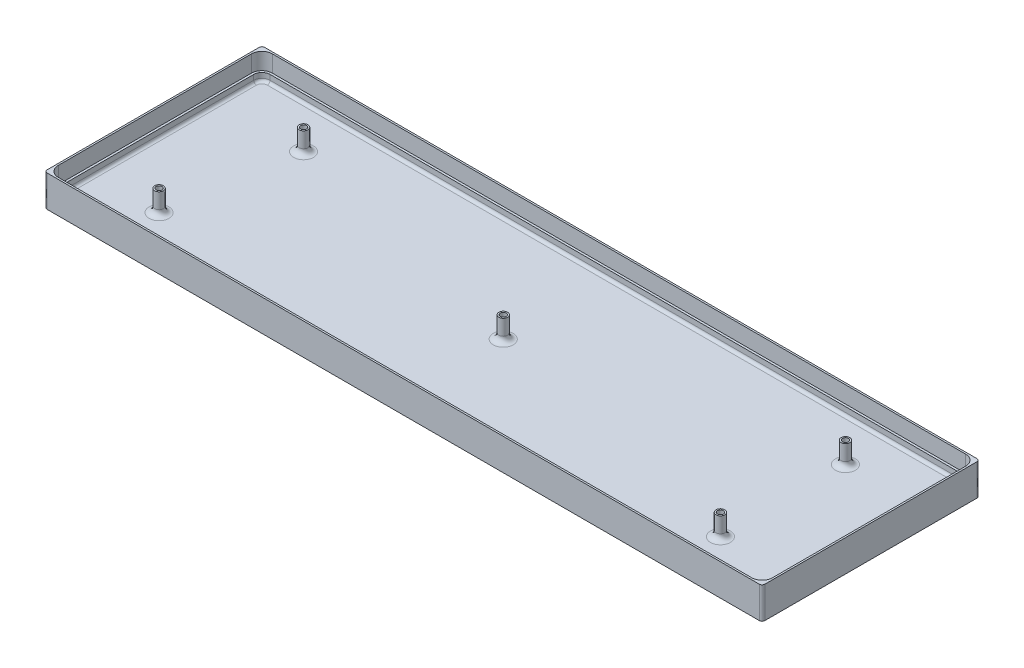
SolidWorks part; units mm, degrees
note: The reader was unsure of these and kept them because the rebuilt part matched: shared geometry of "Sketch1<3>".
ref_plane "Front Plane" through (0, 0, 0) normal (0, 0, 1) x (1, 0, 0)
ref_plane "Top Plane" through (0, 0, 0) normal (0, 1, 0) x (1, 0, 0)
ref_plane "Right Plane" through (0, 0, 0) normal (1, 0, 0) x (0, 0, -1)
sketch "Sketch1" plane through (0, 0, 0) normal (0, 1, 0) x (1, 0, 0)
  line L5 (163.576, 49.5808) -> (-163.576, 49.5808)
  line L6 (162.7759, -48.7807) -> (-162.7759, -48.7807)
  line L10 (162.7759, -48.7807) -> (162.7759, 48.7807)
  line L11 (162.7759, 48.7807) -> (-162.7759, 48.7807)
  line L12 (-162.7759, -48.7807) -> (-162.7759, 48.7807)
  line L13 (162.7759, -48.7807) -> (-162.7759, 48.7807) construction
  line L14 (162.7759, 48.7807) -> (-162.7759, -48.7807) construction
  line L15 (-163.576, -49.5808) -> (-163.576, 49.5808)
  line L16 (163.576, -49.5808) -> (-163.576, -49.5808)
  line L17 (163.576, -49.5808) -> (163.576, 49.5808)
  point P0 (0, 0)
  dimension "D3" = 0.8001
  dimension "D1" = 325.5518
  dimension "D2" = 97.5614
extrude "Boss-Extrude2" add sketch "Sketch1" against normal blind 11.2141
extrude "Boss-Extrude3" add sketch "Sketch1<3>" against normal blind 3.175 from surface at -11.2141 contours L12 L6 L10 L11 | L16 L17 L5 L15 L6 L12 L11 L10 starting at face at (0, -11.2141, 0)
sketch "Sketch1<3>" plane through (0, 0, 0) normal (0, 1, 0) x (1, 0, 0) same geometry as "Sketch1"
fillet "Fillet1" radius 4.7625 4 edges at (162.7759, -5.6071, 48.7807) (162.7759, -5.6071, -48.7807) (-162.7759, -5.6071, 48.7807) (-162.7759, -5.6071, -48.7807)
fillet "Fillet2" radius 1.27 4 edges at (163.576, -7.1945, -49.5808) (163.576, -7.1945, 49.5808) (-163.576, -7.1945, -49.5808) (-163.576, -7.1945, 49.5808)
sketch "Sketch3" plane through (0, -14.3891, 0) normal (0, -1, 0) x (1, 0, 0)
  line L1 (-28.702, 15.5321) -> (28.702, 15.5321)
  line L2 (-30.2895, 13.9446) -> (-30.2895, -13.9446)
  line L3 (-28.702, -15.5321) -> (28.702, -15.5321)
  line L4 (30.2895, 13.9446) -> (30.2895, -13.9446)
  line L5 (-30.2895, 15.5321) -> (30.2895, -15.5321) construction
  line L6 (-30.2895, -15.5321) -> (30.2895, 15.5321) construction
  arc A0 (-28.702, 15.5321) -> (-30.2895, 13.9446) centre (-28.702, 13.9446) ccw
  arc A1 (28.702, 15.5321) -> (30.2895, 13.9446) centre (28.702, 13.9446) cw
  arc A2 (28.702, -15.5321) -> (30.2895, -13.9446) centre (28.702, -13.9446) ccw
  arc A3 (-30.2895, -13.9446) -> (-28.702, -15.5321) centre (-28.702, -13.9446) ccw
  point P0 (0, 0)
  dimension "D3" = 1.5875
  dimension "D1" = 60.579
  dimension "D2" = 31.0642
extrude "Cut-Extrude1" cut sketch "Sketch3" against normal blind 1.5875
sketch "Sketch4" plane through (0, -11.2141, 0) normal (0, 1, 0) x (1, 0, 0)
  circle A0 centre (-123.5, 28.5) radius 2
  circle A1 centre (-123.5, 28.5) radius 1.27 construction
  circle A2 centre (-132.375, -28.5) radius 2
  circle A3 centre (-4, 0) radius 2
  circle A4 centre (123.5, -28.5) radius 2
  circle A5 centre (123.5, 28.5) radius 2
  circle A6 centre (-123.5, 28.5) radius 1.3525
  circle A7 centre (-132.375, -28.5) radius 1.3526
  circle A8 centre (-4, 0) radius 1.3526
  circle A9 centre (123.5, 28.5) radius 1.3525
  circle A10 centre (123.5, -28.5) radius 1.3525
  dimension "D1" = 4
  dimension "D2" = 2.7051
extrude "Boss-Extrude4" add sketch "Sketch4" along normal up to vertex (9.6266 mm away)
sketch "Sketch5" plane through (0, -11.2141, 0) normal (0, 1, 0) x (1, 0, 0)
  line L0 (-158.0134, -47.7647) -> (158.0134, -47.7647)
  line L1 (161.7599, -44.0182) -> (161.7599, 44.0182)
  line L2 (158.0134, 47.7647) -> (-158.0134, 47.7647)
  line L3 (-161.7599, 44.0182) -> (-161.7599, -44.0182)
  line L8 (-158.0134, -48.7807) -> (158.0134, -48.7807)
  line L9 (162.7759, -44.0182) -> (162.7759, 44.0182)
  line L10 (158.0134, 48.7807) -> (-158.0134, 48.7807)
  line L11 (-162.7759, 44.0182) -> (-162.7759, -44.0182)
  line L12 (-158.0134, -48.7807) -> (158.0134, -48.7807)
  line L13 (162.7759, -44.0182) -> (162.7759, 44.0182)
  line L14 (158.0134, 48.7807) -> (-158.0134, 48.7807)
  line L15 (-162.7759, 44.0182) -> (-162.7759, -44.0182)
  arc A0 (158.0134, -47.7647) -> (161.7599, -44.0182) centre (158.0134, -44.0182) ccw
  arc A1 (161.7599, 44.0182) -> (158.0134, 47.7647) centre (158.0134, 44.0182) ccw
  arc A2 (-158.0134, 47.7647) -> (-161.7599, 44.0182) centre (-158.0134, 44.0182) ccw
  arc A3 (-161.7599, -44.0182) -> (-158.0134, -47.7647) centre (-158.0134, -44.0182) ccw
  arc A8 (158.0134, -48.7807) -> (162.7759, -44.0182) centre (158.0134, -44.0182) ccw
  arc A9 (162.7759, 44.0182) -> (158.0134, 48.7807) centre (158.0134, 44.0182) ccw
  arc A10 (-158.0134, 48.7807) -> (-162.7759, 44.0182) centre (-158.0134, 44.0182) ccw
  arc A11 (-162.7759, -44.0182) -> (-158.0134, -48.7807) centre (-158.0134, -44.0182) ccw
  arc A12 (158.0134, -48.7807) -> (162.7759, -44.0182) centre (158.0134, -44.0182) ccw
  arc A13 (162.7759, 44.0182) -> (158.0134, 48.7807) centre (158.0134, 44.0182) ccw
  arc A14 (-158.0134, 48.7807) -> (-162.7759, 44.0182) centre (-158.0134, 44.0182) ccw
  arc A15 (-162.7759, -44.0182) -> (-158.0134, -48.7807) centre (-158.0134, -44.0182) ccw
  dimension "D1" = 0
  dimension "D2" = 1.016
extrude "Boss-Extrude5" add sketch "Sketch5" along normal offset from surface (3.5941 mm away) 7.62 up to face at (0, 0, 0)
fillet "Fillet3" radius 2.54 5 edges at (-123.5, -11.2141, -30.5) (-132.375, -11.2141, 26.5) (-4, -11.2141, -2) (123.5, -11.2141, -30.5) (123.5, -11.2141, 26.5)
fillet "Fillet4" radius 1.27 8 edges at (-160.6626, -11.2141, 46.6674) (-161.7599, -11.2141, 0) (-160.6626, -11.2141, -46.6674) (0, -11.2141, -47.7647) (160.6626, -11.2141, -46.6674) (161.7599, -11.2141, 0) (160.6626, -11.2141, 46.6674) (0, -11.2141, 47.7647)
